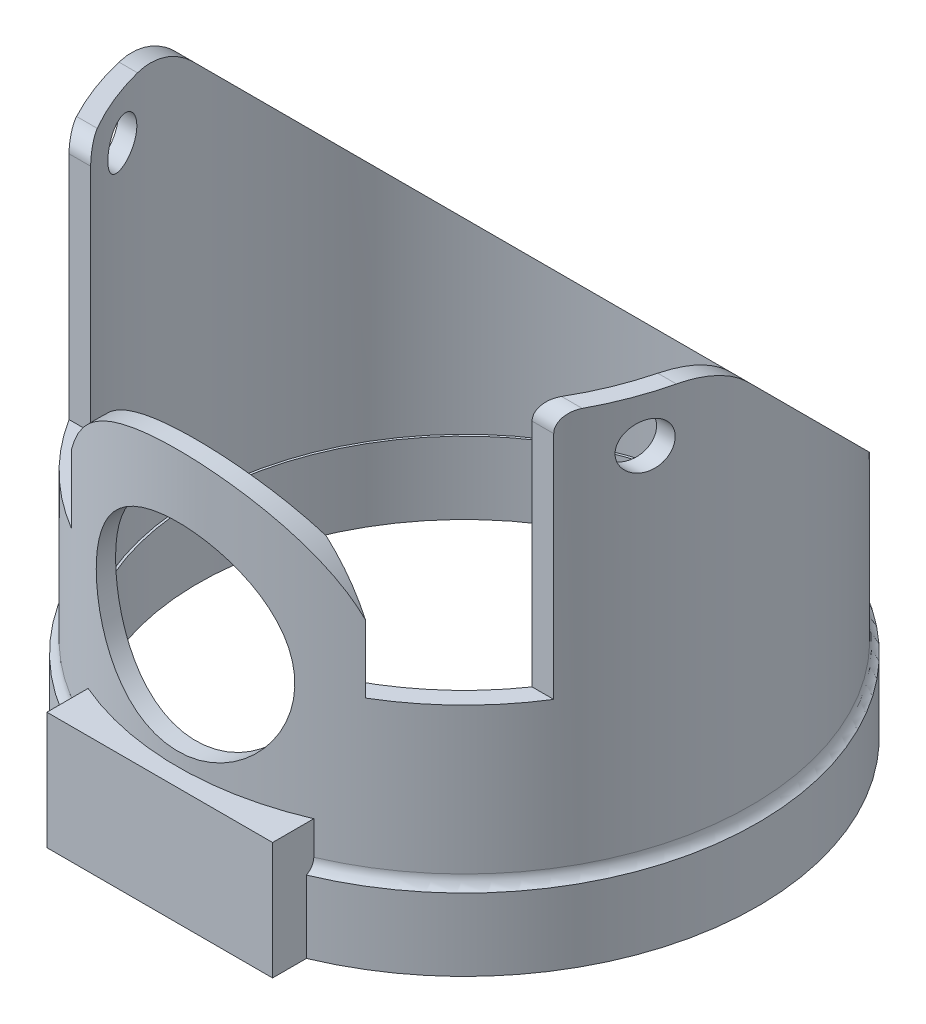
SolidWorks part; units mm, degrees
ref_plane "Спереди" through (0, 0, 0) normal (0, 0, 1) x (1, 0, 0)
ref_plane "Сверху" through (0, 0, 0) normal (0, 1, 0) x (1, 0, 0)
ref_plane "Справа" through (0, 0, 0) normal (1, 0, 0) x (0, 0, -1)
sketch "Эскиз1" plane through (0, 0, 0) normal (0, 1, 0) x (1, 0, 0)
  circle A0 centre (0, 0) radius 32.5
  circle A1 centre (0, 0) radius 29.5
  dimension "D1" = 65
  dimension "D2" = 59
extrude "lower part" add sketch "Эскиз1" along normal blind 8
sketch "Эскиз2" plane through (0, 0, 0) normal (0, -1, 0) x (1, 0, 0)
  circle A0 centre (0, 0) radius 31.5
  circle A1 centre (0, 0) radius 30
  dimension "D1" = 63
  dimension "D2" = 60
extrude "slot" cut sketch "Эскиз2" against normal blind 3
sketch "Эскиз3" plane through (0, 8, 0) normal (0, 1, 0) x (1, 0, 0)
  circle A0 centre (0, 0) radius 31.75
  circle A1 centre (0, 0) radius 29.75
  dimension "D1" = 63.5
  dimension "D2" = 59.5
extrude "higher part" add sketch "Эскиз3" along normal blind 45
sketch "Эскиз4" plane through (0, 0, 0) normal (1, 0, 0) x (0, 0, -1)
  line L0 (31.75, 53) -> (31.75, 18)
  line L1 (31.75, 8) -> (31.75, 53) construction
  line L2 (31.75, 18) -> (-3.25, 53)
  line L3 (29.75, 53) -> (-29.75, 53) construction
  line L4 (-3.25, 53) -> (31.75, 53)
  dimension "D1" = 35
  dimension "D2" = 35
extrude "triangle" cut sketch "Эскиз4" against normal through all and the other way through all
ref_plane "tube start" through (0, 0, 12) normal (0, 0, 1) x (1, 0, 0)
sketch "Эскиз7" plane through (0, 0, 0) normal (1, 0, 0) x (0, 0, -1)
  line L0 (-3.25, 53) -> (-31.75, 53) construction
  line L1 (-16.95, 53) -> (-27.25, 53)
  line L2 (-16.95, 53) -> (-16.95, 25.5)
  line L3 (-16.95, 25.5) -> (-27.25, 25.5)
  line L4 (-27.25, 53) -> (-27.25, 25.5)
  line L5 (-32.5, 0) -> (32.5, 0) construction
  dimension "D1" = 10.3
  dimension "D2" = 25.5
  dimension "D3" = 4.5
extrude "key slot" cut sketch "Эскиз7" against normal up to next and the other way up to next
sketch "Эскиз5" plane through (0, 0, 0) normal (0, 0, 1) x (1, 0, 0)
  line L0 (-32.5, 0) -> (32.5, 0) construction
  circle A0 centre (0, 25.5) radius 11
  dimension "D2" = 22
  dimension "D1" = 25.5
extrude "hole" cut sketch "Эскиз5" along normal through all
sketch "Эскиз9" plane through (0, 0, 0) normal (1, 0, 0) x (0, 0, -1)
  line L0 (0, 0) -> (0, 61.5446) construction
  line L2 (31.5, 3) -> (-31.5, 3) construction
  circle A0 centre (-10, 48) radius 2.5
  dimension "D1" = 5
  dimension "D3" = 10
  dimension "D4" = 45
sketch "Эскиз11" plane through (0, 0, 0) normal (0, 1, 0) x (1, 0, 0)
  line L0 (-12.5, -29.1858) -> (12.5, -29.1858) construction
  line L1 (12.5, -29.1858) -> (12.5, -33.75)
  line L2 (12.5, -33.75) -> (-12.5, -33.75)
  line L3 (-12.5, -33.75) -> (-12.5, -29.1858)
  line L4 (0, 0) -> (0, -31.75) construction
  circle A0 centre (0, 0) radius 31.75 construction
  arc A1 (-16.2942, -27.25) -> (16.2942, -27.25) centre (0, 0) ccw construction
  arc A2 (-12.5, -29.1858) -> (12.5, -29.1858) centre (0, 0) ccw
  dimension "D1" = 25
  dimension "D2" = 2
extrude "support" add sketch "Эскиз11" along normal blind 13
fillet "Скругление1" radius 1.5 1 edges at (0, 8, -31.75)
fillet "Скругление2" radius 10 2 edges at (-30.5776, 53, 3.25) (30.5776, 53, 3.25)
fillet "Скругление3" radius 2 2 edges at (-25.6481, 53, 16.95) (25.6481, 53, 16.95)
sketch "Эскиз12" plane through (0, 0, 0) normal (0, 0, 1) x (1, 0, 0)
  line L0 (16.2942, 25.5) -> (16.2942, 53) construction
  line L1 (-16.2942, 53) -> (16.2942, 53)
  line L4 (16.2942, 53) -> (16.2942, 33)
  line L5 (-16.2942, 53) -> (-16.2942, 33)
  line L6 (-16.2942, 25.5) -> (-16.2942, 53) construction
  arc A0 (-16.2942, 33) -> (16.2942, 33) centre (0, 25.5) cw
  circle A1 centre (0, 25.5) radius 11 construction
  dimension "D1" = 20
extrude "Вытянуть1" cut sketch "Эскиз12" along normal through all
extrude "small hole" cut sketch "Эскиз9" against normal through all and the other way through all
